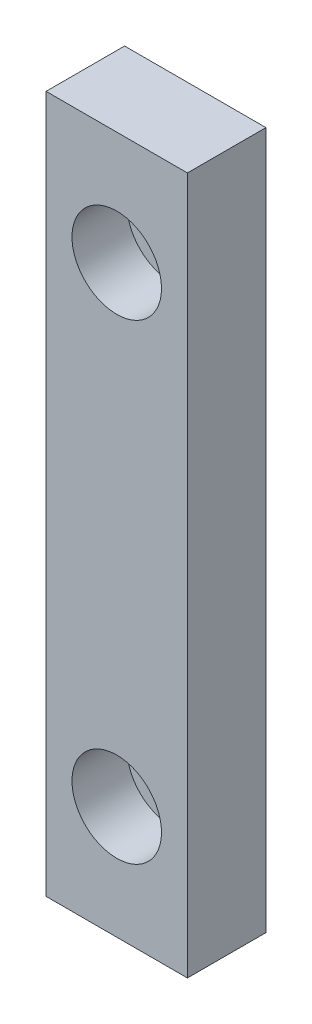
SolidWorks part; units mm, degrees
ref_plane "Front Plane" through (0, 0, 0) normal (1, 0, 0) x (0, 1, 0)
ref_plane "Top Plane" through (0, 0, 0) normal (0, 0, 1) x (0, 1, 0)
ref_plane "Right Plane" through (0, 0, 0) normal (0, 1, 0) x (-1, 0, 0)
sketch "Sketch1" plane through (0, 0, 0) normal (0, 0, 1) x (0, 1, 0)
  line L0 (15, 0) -> (-15, 0) construction
  line L2 (-22.2, 4.5) -> (22.2, 4.5)
  line L3 (-22.2, 4.5) -> (-22.2, -4.5)
  line L4 (-22.2, -4.5) -> (22.2, -4.5)
  line L5 (22.2, 4.5) -> (22.2, -4.5)
  circle A0 centre (-15, 0) radius 1.6
  circle A1 centre (15, 0) radius 1.6
  circle A2 centre (15, 0) radius 2.85
  circle A3 centre (-15, 0) radius 2.85
  point P7 (0, 4.5)
  point P8 (0, 0)
  point P13 (0, 0)
  point P14 (22.2, 0)
  point P15 (20.744, -12.0757)
  dimension "D2" = 3.2
  dimension "D3" = 3.2
  dimension "D4" = 5.7
  dimension "D5" = 5.7
  dimension "D1" = 30
  dimension "D6" = 44.4
  dimension "D7" = 9
extrude "Boss-Extrude1" add sketch "Sketch1" along normal blind 5 contours L5 L2 L3 L4 A2 A3 region at (0, 0, 0)
extrude "Boss-Extrude2" add sketch "Sketch1<3>" along normal blind 1.5 contours A3 A0 | A1 A2 region at (0, 12.2306, 0) region at (0, -17.7694, 0)
sketch "Sketch1<3>" plane through (0, 0, 0) normal (0, 0, 1) x (0, 1, 0) same geometry as "Sketch1"
